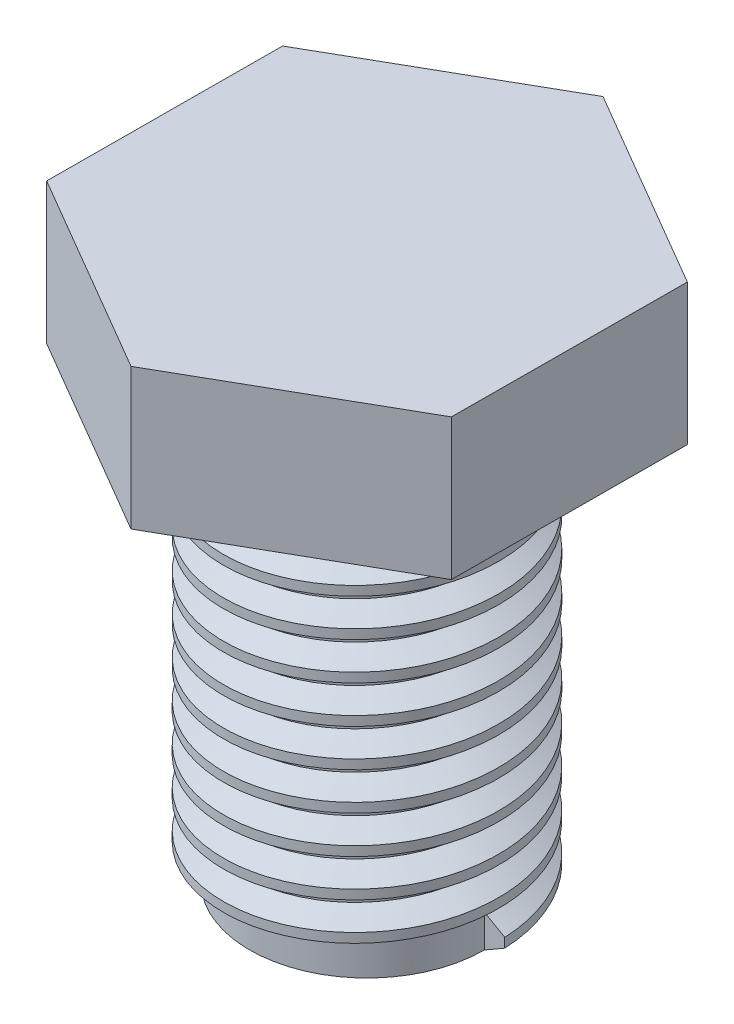
SolidWorks part; units mm, degrees
ref_plane "Front Plane" through (0, 0, 0) normal (0, 0, 1) x (1, 0, 0)
ref_plane "Top Plane" through (0, 0, 0) normal (0, 1, 0) x (1, 0, 0)
ref_plane "Right Plane" through (0, 0, 0) normal (1, 0, 0) x (0, 0, -1)
sketch "Sketch1" plane through (0, 0, 0) normal (0, 1, 0) x (1, 0, 0)
  circle A0 centre (0, 0) radius 12.5
  dimension "D1" = 25
extrude "Boss-Extrude1" add sketch "Sketch1" along normal blind 45
sketch "Sketch2" plane through (0, 45, 0) normal (0, 1, 0) x (1, 0, 0)
  line L1 (21.5887, -12.6067) -> (21.7121, 12.3929)
  line L2 (21.7121, 12.3929) -> (0.1234, 24.9997)
  line L3 (0.1234, 24.9997) -> (-21.5887, 12.6067)
  line L4 (-21.5887, 12.6067) -> (-21.7121, -12.3929)
  line L5 (-21.7121, -12.3929) -> (-0.1234, -24.9997)
  line L6 (-0.1234, -24.9997) -> (21.5887, -12.6067)
  circle A0 centre (0, 0) radius 21.6506 construction
  dimension "D1" = 25
extrude "Boss-Extrude2" add sketch "Sketch2" along normal blind 15
thread "Thread1" pitch 4 method extrude profile "Thread Profile1" start angle 0, offset 0, length 0, pitch 4, diameter 25
ref_plane "Plane1" through (12.5, 0, 0) normal (0, 0, -1) x (-1, 0, 0)
sketch "Thread Profile1" plane through (12.5, 0, 0) normal (0, 0, -1) x (-1, 0, 0)
  line L0 (0, 0) -> (0, 4) construction
  line L11 (0, 0) -> (0, 3.5)
  line L12 (0, 3.5) -> (-2.1651, 2.25)
  line L13 (-2.1651, 2.25) -> (-2.1651, 1.25)
  line L15 (-2.1651, 1.25) -> (0, 0)
  line L17 (-2.1651, 1.75) -> (0, 1.75) construction
  point P2 (0, 0)
  dimension "Pitch" = 4
  dimension "Profile_Angle" = 60
  dimension "Profile_Land" = 1
  dimension "Profile_Height" = 2.1651
